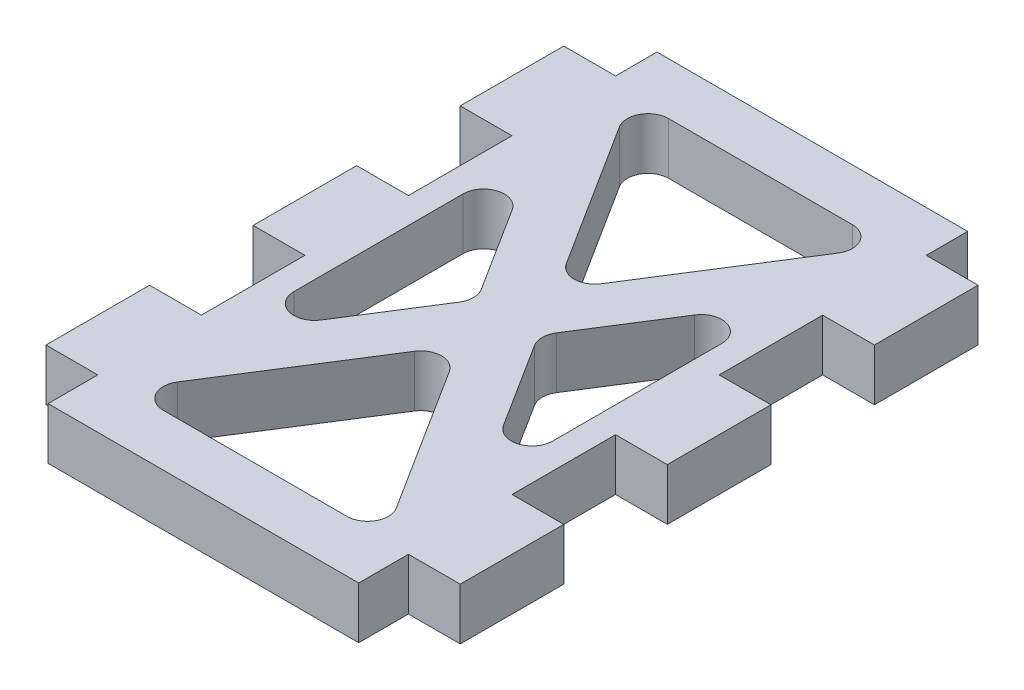
SolidWorks part; units mm, degrees
material "Custom Plastic"
ref_plane "Front Plane" through (0, 0, 0) normal (0, 0, 1) x (1, 0, 0)
ref_plane "Top Plane" through (0, 0, 0) normal (0, 1, 0) x (1, 0, 0)
ref_plane "Right Plane" through (0, 0, 0) normal (1, 0, 0) x (0, 0, -1)
sketch "Sketch1" plane through (0, 0, 0) normal (0, 1, 0) x (1, 0, 0)
  line L1 (25.4, -37.338) -> (-25.4, -37.338)
  line L2 (25.4, -37.338) -> (25.4, 37.338)
  line L3 (25.4, 37.338) -> (-25.4, 37.338)
  line L4 (-25.4, -37.338) -> (-25.4, 37.338)
  line L5 (25.4, -37.338) -> (-25.4, 37.338) construction
  line L6 (25.4, 37.338) -> (-25.4, -37.338) construction
  point P0 (0, 0)
  dimension "D1" = 74.676
  dimension "D2" = 50.8
extrude "Main" add sketch "Sketch1" along normal blind 6.35
sketch "Sketch2" plane through (0, 6.35, 0) normal (0, 1, 0) x (1, 0, 0)
  line L0 (25.4, -37.338) -> (25.4, 37.338) construction
  line L1 (25.4, 32.258) -> (19.05, 32.258)
  line L2 (25.4, 32.258) -> (25.4, 19.558) construction
  line L3 (25.4, 19.558) -> (19.05, 19.558)
  line L4 (19.05, 32.258) -> (19.05, 19.558) construction
  line L5 (25.4, 19.558) -> (25.4, 6.858)
  line L6 (25.4, 6.858) -> (19.05, 6.858)
  line L7 (25.4, 6.858) -> (25.4, -5.842) construction
  line L8 (25.4, -5.842) -> (19.05, -5.842)
  line L9 (19.05, 6.858) -> (19.05, -5.842) construction
  line L10 (25.4, -18.542) -> (19.05, -18.542)
  line L11 (25.4, -18.542) -> (25.4, -31.242) construction
  line L12 (25.4, -31.242) -> (19.05, -31.242)
  line L13 (19.05, -18.542) -> (19.05, -31.242) construction
  line L14 (25.4, -5.842) -> (25.4, -18.542)
  line L15 (25.4, 37.338) -> (-25.4, 37.338) construction
  line L16 (0, 37.338) -> (0, -37.338) construction
  line L17 (-25.4, -37.338) -> (25.4, -37.338) construction
  line L18 (-19.05, -18.542) -> (-19.05, -31.242) construction
  line L19 (-25.4, -18.542) -> (-25.4, -31.242) construction
  line L20 (-19.05, 6.858) -> (-19.05, -5.842) construction
  line L21 (-25.4, 6.858) -> (-25.4, -5.842) construction
  line L22 (-19.05, 32.258) -> (-19.05, 19.558) construction
  line L23 (-25.4, 32.258) -> (-25.4, 19.558) construction
  line L24 (-25.4, -37.338) -> (-25.4, -31.242)
  line L25 (-19.05, -37.338) -> (-25.4, -37.338)
  line L26 (-19.05, -31.242) -> (-19.05, -37.338)
  line L27 (-19.05, -5.842) -> (-19.05, -18.542)
  line L28 (-19.05, 19.558) -> (-19.05, 6.858)
  line L29 (-25.4, 37.338) -> (-25.4, 32.258)
  line L30 (-19.05, 37.338) -> (-25.4, 37.338)
  line L31 (-19.05, 32.258) -> (-19.05, 37.338)
  line L32 (19.05, 32.258) -> (19.05, 37.338)
  line L33 (19.05, 37.338) -> (25.4, 37.338)
  line L34 (25.4, 37.338) -> (25.4, 32.258)
  line L35 (19.05, 19.558) -> (19.05, 6.858)
  line L36 (19.05, -5.842) -> (19.05, -18.542)
  line L37 (19.05, -31.242) -> (19.05, -37.338)
  line L38 (19.05, -37.338) -> (25.4, -37.338)
  line L39 (25.4, -37.338) -> (25.4, -31.242)
  line L40 (-25.4, -5.842) -> (-25.4, -18.542)
  line L41 (-25.4, -31.242) -> (-19.05, -31.242)
  line L42 (-25.4, -18.542) -> (-19.05, -18.542)
  line L43 (-25.4, -5.842) -> (-19.05, -5.842)
  line L44 (-25.4, 6.858) -> (-19.05, 6.858)
  line L45 (-25.4, 19.558) -> (-25.4, 6.858)
  line L46 (-25.4, 19.558) -> (-19.05, 19.558)
  line L47 (-25.4, 32.258) -> (-19.05, 32.258)
  dimension "D1" = 12.7
  dimension "D2" = 5.08
  dimension "D3" = 6.35
extrude "Acrylic Mounts" cut sketch "Sketch2" against normal through all
sketch "Sketch3" plane through (0, 6.35, 0) normal (0, 1, 0) x (1, 0, 0)
  line L0 (-15.875, 30.988) -> (0, 5.9323)
  line L1 (0, 5.9323) -> (15.875, 30.988)
  line L2 (15.875, 30.988) -> (-15.875, 30.988)
  line L3 (-15.875, 19.1234) -> (-3.7586, 0)
  line L4 (-3.7586, 0) -> (-15.875, -19.1234)
  line L5 (-15.875, -19.1234) -> (-15.875, 19.1234)
  line L6 (-15.875, -30.988) -> (0, -5.9323)
  line L7 (0, -5.9323) -> (15.875, -30.988)
  line L8 (15.875, -30.988) -> (-15.875, -30.988)
  line L9 (15.875, -19.1234) -> (3.7586, 0)
  line L10 (3.7586, 0) -> (15.875, 19.1234)
  line L11 (15.875, 19.1234) -> (15.875, -19.1234)
  line L12 (19.05, 37.338) -> (-19.05, 37.338) construction
  line L13 (19.05, 19.558) -> (19.05, 6.858) construction
  line L14 (-19.05, 6.858) -> (-19.05, 19.558) construction
  line L15 (-19.05, -37.338) -> (19.05, -37.338) construction
  dimension "D1" = 6.35
  dimension "D2" = 3.175
  dimension "D3" = 3.175
  dimension "D4" = 6.35
  dimension "D5" = 6.35
extrude "Cut-Extrude2" cut sketch "Sketch3" against normal through all
fillet "Fillet1" radius 2.54 12 edges at (15.875, 3.175, 30.988) (15.875, 3.175, 19.1234) (-15.875, 3.175, 30.988) (-15.875, 3.175, 19.1234) (0, 3.175, -5.9323) (-15.875, 3.175, -19.1234) (0, 3.175, 5.9323) (-3.7586, 3.175, 0) (15.875, 3.175, -19.1234) (15.875, 3.175, -30.988) (3.7586, 3.175, 0) (-15.875, 3.175, -30.988)
